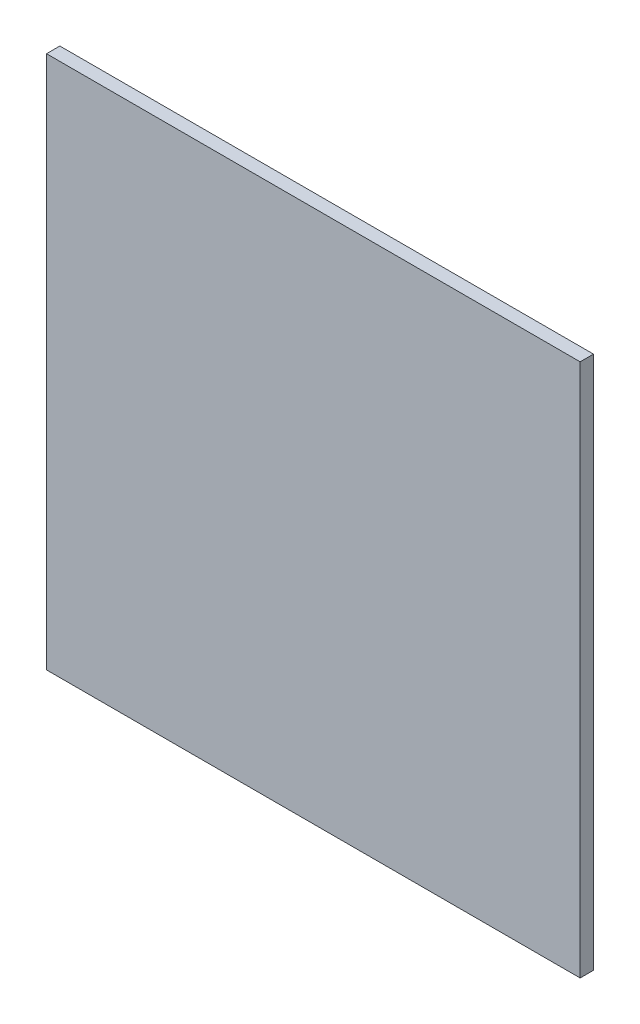
SolidWorks part; units mm, degrees
ref_plane "Front Plane" through (0, 0, 0) normal (0, 0, 1) x (1, 0, 0)
ref_plane "Top Plane" through (0, 0, 0) normal (0, 1, 0) x (1, 0, 0)
ref_plane "Right Plane" through (0, 0, 0) normal (1, 0, 0) x (0, 0, -1)
sketch "Esquisse1" plane through (0, 0, 0) normal (0, 0, 1) x (1, 0, 0)
  line L1 (-200, 200) -> (200, 200)
  line L2 (-200, 200) -> (-200, -200)
  line L3 (-200, -200) -> (200, -200)
  line L4 (200, 200) -> (200, -200)
  point P4 (0, 0)
  point P5 (-200, 0)
  point P7 (0, 200)
  dimension "D1" = 400
  dimension "D2" = 400
extrude "Boss.-Extru.1" add sketch "Esquisse1" along normal blind 10
